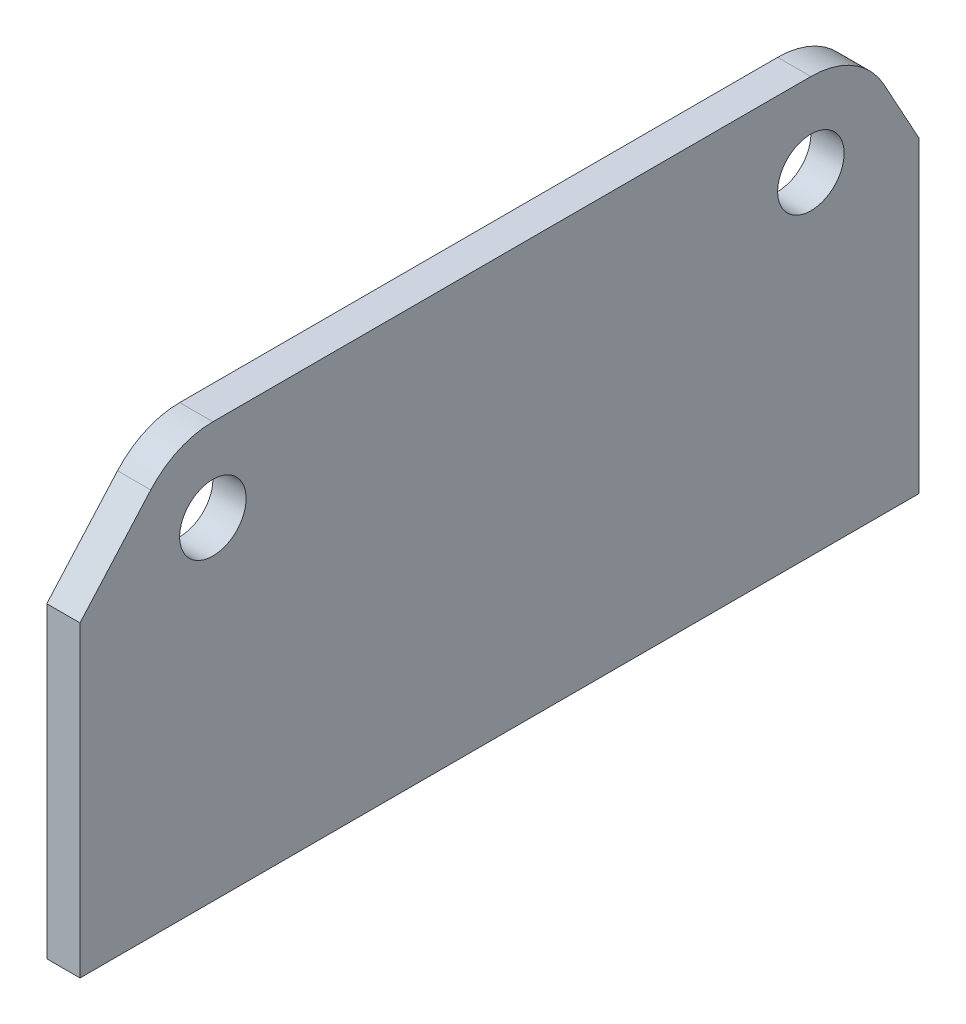
SolidWorks part; units mm, degrees
material "6061-T6 (SS)"
ref_plane "Front Plane" through (0, 0, 0) normal (0, 0, 1) x (1, 0, 0)
ref_plane "Top Plane" through (0, 0, 0) normal (0, 1, 0) x (1, 0, 0)
ref_plane "Right Plane" through (0, 0, 0) normal (1, 0, 0) x (0, 0, -1)
sketch "Sketch1" plane through (0, 0, 0) normal (1, 0, 0) x (0, 0, -1)
  line L0 (0, 44.45) -> (0, 0) construction
  line L1 (-279.4, 44.45) -> (279.4, 44.45)
  line L2 (-279.4, 44.45) -> (-279.4, -44.45)
  line L3 (-279.4, -44.45) -> (279.4, -44.45)
  line L4 (279.4, 44.45) -> (279.4, -44.45)
  line L5 (0, 0) -> (279.4, 0) construction
  dimension "D1" = 558.8
  dimension "D2" = 88.9
extrude "Boss-Extrude1" add sketch "Sketch1" along normal blind 12.7 contours L4 L1 L2 L3 region at (0, 0, 0)
sketch "Sketch2" plane through (12.7, 0, 0) normal (1, 0, 0) x (0, 0, -1)
  line L0 (-279.4, -44.45) -> (279.4, -44.45) construction
  line L1 (-279.4, 44.45) -> (-226.9595, 103.6106)
  line L2 (82.55, 44.45) -> (53.2287, 97.8348)
  line L3 (-203.2, 114.3) -> (25.4, 114.3)
  line L4 (-279.4, 44.45) -> (82.55, 44.45)
  line L5 (-279.4, 44.45) -> (279.4, 44.45) construction
  line L6 (279.4, 44.45) -> (279.4, -44.45) construction
  line L7 (-279.4, 44.45) -> (-318.8009, 0) construction
  line L8 (-318.8009, 0) -> (-279.4, -44.45) construction
  line L9 (-279.4, 44.45) -> (-279.4, -44.45) construction
  line L10 (-279.4, -44.45) -> (-279.4, 0) construction
  line L11 (-279.4, 0) -> (-318.8009, 0) construction
  circle A0 centre (-203.2, 82.55) radius 12.7
  circle A1 centre (25.4, 82.55) radius 12.7
  circle A2 centre (-203.2, 82.55) radius 31.75
  circle A3 centre (25.4, 82.55) radius 31.75
  line M2 (279.4, 44.45) -> (-279.4, 44.45)
  dimension "D1" = 25.4
  dimension "D2" = 63.5
  dimension "D3" = 127
  dimension "D4" = 127
  dimension "D5" = 228.6
  dimension "D6" = 254
  dimension "D7" = 196.85
extrude "Boss-Extrude2" add sketch "Sketch2" against normal blind 12.7 contours A3 L3 A2 L1 L2 M2 | A2 A0 | A3 A1 region at (12.7, 75.2348, 94.7711) region at (12.7, 110.6856, 215.8582) region at (12.7, 90.2167, -55.2842)
sketch "Sketch3" plane through (12.7, 0, 0) normal (1, 0, 0) x (0, 0, -1)
  line L0 (-279.4, -44.45) -> (-318.8009, 0)
  line L1 (-318.8009, 0) -> (-279.4, 44.45)
  line L2 (-279.4, 44.45) -> (-279.4, -44.45)
  line L3 (-318.8009, 0) -> (-279.4, 0) construction
  line L4 (-279.4, 44.45) -> (-226.9595, 103.6106) construction
extrude "Boss-Extrude3" add sketch "Sketch3" against normal blind 12.7
sketch "Sketch4" plane through (12.7, 0, 0) normal (1, 0, 0) x (0, 0, -1)
  line L0 (82.55, 44.45) -> (106.9639, 0)
  line L1 (106.9639, 0) -> (82.55, -44.45)
  line L2 (-279.4, -44.45) -> (279.4, -44.45) construction
  line L3 (0, 0) -> (106.9639, 0) construction
  line L4 (82.55, 44.45) -> (53.2287, 97.8348) construction
  line L5 (82.55, 44.45) -> (279.4, 44.45)
  line L6 (279.4, 44.45) -> (279.4, -44.45)
  line L7 (279.4, -44.45) -> (82.55, -44.45)
  line L8 (82.55, 44.45) -> (82.55, -44.45) construction
extrude "Cut-Extrude1" cut sketch "Sketch4" against normal through all
sketch "Sketch5" plane through (12.7, 0, 0) normal (1, 0, 0) x (0, 0, -1)
  line L0 (-254, -44.45) -> (-254, 73.1049)
  line L1 (-279.4, -44.45) -> (82.55, -44.45) construction
  line L2 (-318.8009, 0) -> (-226.9595, 103.6106) construction
  line L3 (-254, 73.1049) -> (66.8114, 73.1049) construction
  line L4 (-254, -44.45) -> (-279.4, -44.45)
  line L5 (-279.4, -44.45) -> (-318.8009, 0)
  line L6 (-318.8009, 0) -> (-254, 73.1049)
  line L7 (66.8114, 73.1049) -> (66.8114, -44.45)
  line L8 (106.9639, 0) -> (53.2287, 97.8348) construction
  line L9 (66.8114, -44.45) -> (82.55, -44.45)
  line L10 (82.55, -44.45) -> (106.9639, 0)
  line L11 (106.9639, 0) -> (66.8114, 73.1049)
  circle A0 centre (-203.2, 82.55) radius 12.7 construction
  dimension "D1" = 50.8
extrude "Cut-Extrude2" cut sketch "Sketch5" against normal through all
